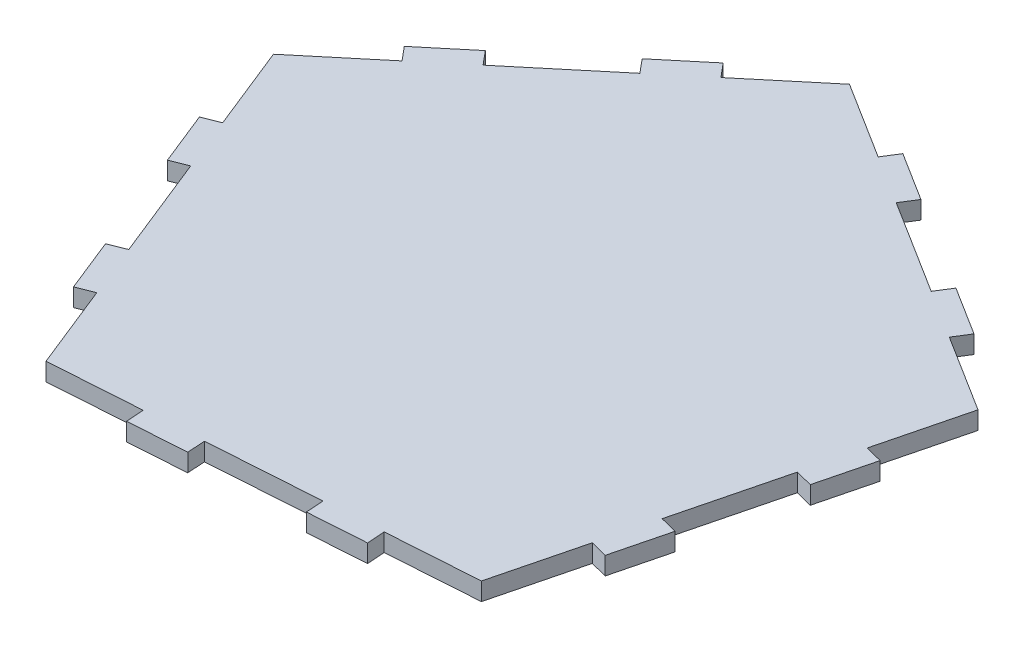
SolidWorks part; units mm, degrees
ref_plane "Front Plane" through (0, 0, 0) normal (0, 0, 1) x (1, 0, 0)
ref_plane "Top Plane" through (0, 0, 0) normal (0, 1, 0) x (1, 0, 0)
ref_plane "Right Plane" through (0, 0, 0) normal (1, 0, 0) x (0, 0, -1)
sketch "Sketch1" plane through (0, 0, 0) normal (0, 1, 0) x (1, 0, 0)
  line L1 (-59.9258, 15.1181) -> (-32.8962, -52.3211)
  line L2 (-32.8962, -52.3211) -> (39.5948, -47.4543)
  line L3 (39.5948, -47.4543) -> (57.3672, 22.9927)
  line L4 (57.3672, 22.9927) -> (-4.14, 61.6646)
  line L5 (-4.14, 61.6646) -> (-59.9258, 15.1181)
  circle A0 centre (0, 0) radius 50 construction
  dimension "D1" = 100
extrude "Boss-Extrude1" add sketch "Sketch1" along normal blind 3.18
ref_axis "Axis" through (0, 3.339, 0) along (0, -1, 0)
sketch "Axis Check" plane through (0, 3.18, 0) normal (0, 1, 0) x (1, 0, 0)
  line L0 (3.3493, -49.8877) -> (-4.14, 61.6646) construction
  line L1 (-32.8962, -52.3211) -> (39.5948, -47.4543) construction
  line L2 (57.3672, 22.9927) -> (-46.411, -18.6015) construction
  line L3 (-59.9258, 15.1181) -> (-32.8962, -52.3211) construction
  line L4 (-32.0329, 38.3913) -> (39.5948, -47.4543) construction
  line L5 (-4.14, 61.6646) -> (-59.9258, 15.1181) construction
  line L6 (-59.9258, 15.1181) -> (48.481, -12.2308) construction
  line L7 (39.5948, -47.4543) -> (57.3672, 22.9927) construction
  line L8 (-32.8962, -52.3211) -> (26.6136, 42.3287) construction
  line L9 (57.3672, 22.9927) -> (-4.14, 61.6646) construction
sketch "Sketch2" plane through (0, 0, 0) normal (0, -1, 0) x (1, 0, 0)
  line L0 (-53.8107, 0.1392) -> (-50.859, -1.0438)
  line L1 (-53.8107, 0.1392) -> (-50.1723, 9.2172)
  line L2 (-50.859, -1.0438) -> (-47.2205, 8.0342)
  line L3 (-50.1723, 9.2172) -> (-47.2205, 8.0342)
  line L4 (-59.9258, -15.1181) -> (-32.8962, 52.3211) construction
  line L5 (-42.6498, 27.9858) -> (-39.0113, 37.0638)
  line L6 (-42.6498, 27.9858) -> (-39.6981, 26.8028)
  line L7 (-39.0113, 37.0638) -> (-36.0596, 35.8808)
  line L8 (-39.6981, 26.8028) -> (-36.0596, 35.8808)
  line L9 (-46.411, 18.6015) -> (-19.2439, 7.7129) construction
  line L10 (-40.8306, 32.5248) -> (-37.8788, 31.3418) construction
  dimension "D1" = 3.18
  dimension "D2" = 9.78
  dimension "D3" = 10.11
extrude "Cut F" [suppressed] cut sketch "Sketch2" against normal through all
sketch "Sketch4" [suppressed] plane through (0, 3.18, 0) normal (0, 1, 0) x (1, 0, 0)
  line L9 (26.6136, 42.3287) -> (-26.6136, -42.3287) construction
  line L10 (57.3672, 22.9927) -> (-4.14, 61.6646) construction
  line L11 (-27.5764, -6.9547) -> (-6.9547, 27.5764)
  line L12 (-27.5764, -6.9547) -> (6.9547, -27.5764)
  line L13 (-6.9547, 27.5764) -> (27.5764, 6.9547)
  line L14 (6.9547, -27.5764) -> (27.5764, 6.9547)
  line L15 (-27.5764, -6.9547) -> (27.5764, 6.9547) construction
  line L16 (-6.9547, 27.5764) -> (6.9547, -27.5764) construction
  point P5 (0, 0)
  dimension "D1" = 40.22
  dimension "D2" = 40.22
extrude "Top Cut" [suppressed] cut sketch "Sketch4" against normal blind 10
sketch "Sketch3" plane through (0, 3.18, 0) normal (0, 1, 0) x (1, 0, 0)
  line L0 (0, 0) -> (-40.9819, 49.1167) construction
  line L1 (-49.5112, 27.9494) -> (-45.4366, 23.066)
  line L3 (-45.4366, 23.066) -> (-37.5894, 29.6135)
  line L4 (-41.664, 34.4969) -> (-37.5894, 29.6135)
  line L5 (-4.14, 61.6646) -> (-59.9258, 15.1181) construction
  line L6 (-71.9961, 5.0469) -> (-69.9588, 2.6052)
  line L7 (-71.9961, 5.0469) -> (-47.4739, 25.5077)
  line L14 (-26.4764, 47.1691) -> (-22.4018, 42.2857)
  line L16 (-22.4018, 42.2857) -> (-14.5546, 48.8333)
  line L17 (-18.6292, 53.7166) -> (-14.5546, 48.8333)
  line L18 (-42.539, 27.5695) -> (-41.513, 26.3398) construction
  line L19 (-49.5112, 27.9494) -> (-41.664, 34.4969)
  line L21 (-26.4764, 47.1691) -> (-18.6292, 53.7166)
  line L22 (-16.5919, 51.275) -> (4.7866, 69.1127)
  line L23 (-39.6267, 32.0552) -> (-24.4391, 44.7274)
  line M18 (-4.14, 61.6646) -> (-59.9258, 15.1181)
  dimension "D1" = 3.18
  dimension "D2" = 10.22
  dimension "D3" = 9.89
  dimension "D4" = 100
extrude "Extrude M" add sketch "Sketch3" against normal up to surface (3.18 mm away) contours L21 L14 L7 L17 | L19 L1 L4 M18 region at (-44.5689, 3.18, -30.0023) region at (-21.5341, 3.18, -49.222) up to face at (0, 0, 0)
pattern_circular "Circle F" [suppressed] count 5 over 360 about axis through (0, 3.339, 0) along (0, -1, 0) of bodies 173
pattern_circular "Circle M" count 5 over 360 about axis through (0, 3.339, 0) along (0, -1, 0) of "Extrude M"
pattern_circular "Circle Side F" [suppressed] count 5 over 360 about axis through (0, 3.339, 0) along (0, -1, 0) of bodies 173
pattern_circular "Circle Side M" [suppressed] count 5 over 360 about axis through (0, 3.339, 0) along (0, -1, 0) of bodies 168
equation "\"kerf\"= .22mm"
equation "\"tabWidthF\"= 10 - \"kerf\""
equation "\"tabThickness\"= 3.18"
equation "\"D1@Sketch2\"=\"tabThickness\""
equation "\"tabWidthM\"= 10 + \"kerf\""
equation "\"halfkerf\"= \"kerf\" / 2.00mm"
equation "\"tabLength\" = \"kerf\" + 12"
